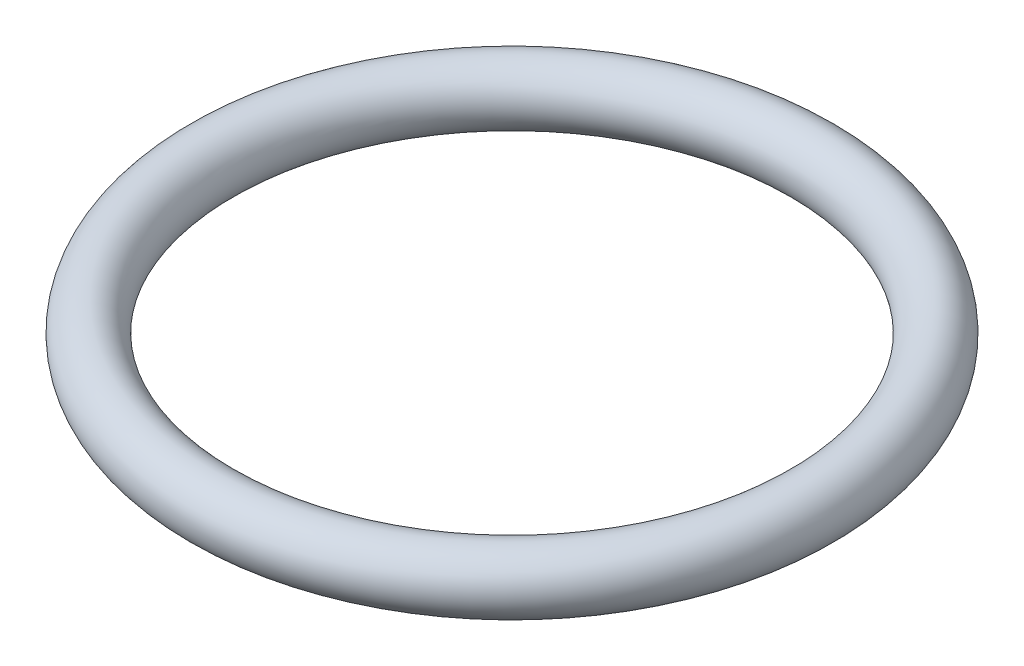
SolidWorks part; units mm, degrees
ref_plane "Front" through (0, 0, 0) normal (0, 0, 1) x (1, 0, 0)
ref_plane "Top" through (0, 0, 0) normal (0, 1, 0) x (1, 0, 0)
ref_plane "Right" through (0, 0, 0) normal (1, 0, 0) x (0, 0, -1)
sketch "Sketch1" plane through (0, 0, 0) normal (0, 0, 1) x (1, 0, 0)
  line L0 (0, 14.0803) -> (0, -13.5453) construction
  line L1 (-13.2918, 0) -> (15.7418, 0) construction
  circle A0 centre (-10, 0) radius 1
  dimension "D1" = 2
  dimension "D2" = 10
revolve "Revolve1" add sketch "Sketch1" angle 360 about L0
ref_axis "Axis1" through (0, 4.752, 0) along (0, -1, 0)
